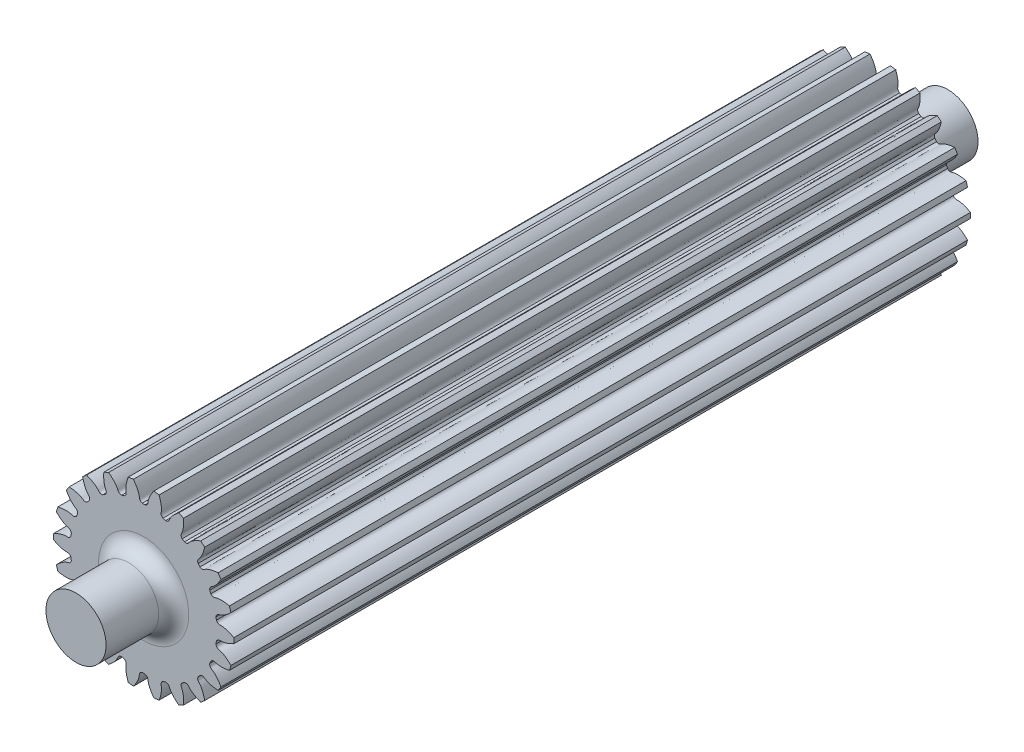
SolidWorks part; units mm, degrees
ref_plane "前视基准面" through (0, 0, 0) normal (0, 0, 1) x (1, 0, 0)
ref_plane "上视基准面" through (0, 0, 0) normal (0, 1, 0) x (1, 0, 0)
ref_plane "右视基准面" through (0, 0, 0) normal (1, 0, 0) x (0, 0, -1)
sketch "草图1" plane through (0, 0, 0) normal (0, 0, 1) x (1, 0, 0)
  circle A0 centre (0, 0) radius 12
extrude "凸台-拉伸1" add sketch "草图1" along normal blind 30
ref_axis "基准轴1" through (0, 0, -1.5) along (0, 0, 1)
sketch "草图2" plane through (0, 0, 0) normal (0, 0, 1) x (1, 0, 0)
  line L0 (0, 0) -> (0, 12) construction
  circle A0 centre (0, 0) radius 12 construction
  arc A1 (0.1857, 9.7482) -> (-0.1857, 9.7482) centre (0, 0) ccw
  arc A2 (3.0856, 13.5599) -> (-3.0856, 13.5599) centre (0, 0) ccw
  spline S0 degree 3 poles (0.1857, 9.7482) (0.5882, 9.8762) (0.5483, 10.1518) (0.5996, 10.4216) (0.606, 10.4519) (0.6139, 10.4862) (0.6235, 10.5243) (0.6349, 10.5661) (0.6484, 10.6117) (0.664, 10.661) (0.6819, 10.7139) (0.7023, 10.7703) (0.7253, 10.8301) (0.7511, 10.8933) (0.7797, 10.9597) (0.8114, 11.0293) (0.8462, 11.1021) (0.8843, 11.1778) (0.9259, 11.2563) (0.9711, 11.3377) (1.0199, 11.4217) (1.0726, 11.5082) (1.1292, 11.5972) (1.1899, 11.6884) (1.2547, 11.7818) (1.3238, 11.8773) (1.3973, 11.9746) (1.4753, 12.0737) (1.5579, 12.1744) (1.6452, 12.2766) (1.7372, 12.3802) (1.8341, 12.4849) (1.9359, 12.5906) (2.0428, 12.6972) (2.1547, 12.8044) (2.2718, 12.9123) (2.3942, 13.0205) (2.5218, 13.1289) (2.6548, 13.2373) (2.8415, 13.3834) (2.9864, 13.49) (3.0856, 13.5599) knots 0 0 0 0 0.157021 0.162531 0.168888 0.176093 0.184146 0.193046 0.202794 0.213389 0.224833 0.237123 0.250262 0.264248 0.279082 0.294763 0.311292 0.328669 0.346893 0.365965 0.385884 0.406652 0.428266 0.450729 0.474039 0.498197 0.523202 0.549055 0.575756 0.603304 0.6317 0.660944 0.691035 0.721974 0.75376 0.786395 0.819876 0.854206 0.889383 0.925408 1 1 1 1
  spline S1 degree 3 poles (-0.1857, 9.7482) (-0.5882, 9.8762) (-0.5483, 10.1518) (-0.5996, 10.4216) (-0.606, 10.4519) (-0.6139, 10.4862) (-0.6235, 10.5243) (-0.6349, 10.5661) (-0.6484, 10.6117) (-0.664, 10.661) (-0.6819, 10.7139) (-0.7023, 10.7703) (-0.7253, 10.8301) (-0.7511, 10.8933) (-0.7797, 10.9597) (-0.8114, 11.0293) (-0.8462, 11.1021) (-0.8843, 11.1778) (-0.9259, 11.2563) (-0.9711, 11.3377) (-1.0199, 11.4217) (-1.0726, 11.5082) (-1.1292, 11.5972) (-1.1899, 11.6884) (-1.2547, 11.7818) (-1.3238, 11.8773) (-1.3973, 11.9746) (-1.4753, 12.0737) (-1.5579, 12.1744) (-1.6452, 12.2766) (-1.7372, 12.3802) (-1.8341, 12.4849) (-1.9359, 12.5906) (-2.0428, 12.6972) (-2.1547, 12.8044) (-2.2718, 12.9123) (-2.3942, 13.0205) (-2.5218, 13.1289) (-2.6548, 13.2373) (-2.8415, 13.3834) (-2.9864, 13.49) (-3.0856, 13.5599) knots 0 0 0 0 0.157021 0.162531 0.168888 0.176093 0.184146 0.193046 0.202794 0.213389 0.224833 0.237123 0.250262 0.264248 0.279082 0.294763 0.311292 0.328669 0.346893 0.365965 0.385884 0.406652 0.428266 0.450729 0.474039 0.498197 0.523202 0.549055 0.575756 0.603304 0.6317 0.660944 0.691035 0.721974 0.75376 0.786395 0.819876 0.854206 0.889383 0.925408 1 1 1 1
extrude "切除-拉伸1" cut sketch "草图2" along normal through all
pattern_circular "阵列(圆周)1" count 22 every 16.364 about axis through (0, 0, -1.5) along (0, 0, 1) of "切除-拉伸1"
sketch "草图3" plane through (0, 0, 0) normal (0, 0, 1) x (1, 0, 0)
  circle A0 centre (0, 0) radius 11 construction
  dimension "Dn" = 22
sketch "草图4" plane through (0, 0, 0) normal (0, 0, -1) x (-1, 0, 0)
  arc A45 (2.9245, 9.3011) -> (2.5682, 9.4057) centre (0, 0) ccw
  arc A46 (2.0557, 11.8226) -> (1.3584, 11.9229) centre (0, 0) ccw
  arc A47 (0.1857, 9.7482) -> (-0.1857, 9.7482) centre (0, 0) ccw
  arc A48 (-1.3584, 11.9229) -> (-2.0557, 11.8226) centre (0, 0) ccw
  arc A49 (-2.5682, 9.4057) -> (-2.9245, 9.3011) centre (0, 0) ccw
  arc A50 (-4.6624, 11.0572) -> (-5.3032, 10.7646) centre (0, 0) ccw
  arc A51 (-5.1141, 8.3011) -> (-5.4265, 8.1004) centre (0, 0) ccw
  arc A52 (-7.5887, 9.2958) -> (-8.1211, 8.8344) centre (0, 0) ccw
  arc A53 (-7.2456, 6.5241) -> (-7.4888, 6.2434) centre (0, 0) ccw
  arc A54 (-9.9003, 6.7812) -> (-10.2811, 6.1886) centre (0, 0) ccw
  arc A55 (-8.7902, 4.2184) -> (-8.9444, 3.8807) centre (0, 0) ccw
  arc A56 (-11.4097, 3.7173) -> (-11.6082, 3.0414) centre (0, 0) ccw
  arc A57 (-9.6226, 1.5711) -> (-9.6754, 1.2035) centre (0, 0) ccw
  arc A58 (-11.9948, 0.3522) -> (-11.9948, -0.3522) centre (0, 0) ccw
  arc A59 (-9.6754, -1.2035) -> (-9.6226, -1.5711) centre (0, 0) ccw
  arc A60 (-11.6082, -3.0414) -> (-11.4097, -3.7173) centre (0, 0) ccw
  arc A61 (-8.9444, -3.8807) -> (-8.7902, -4.2184) centre (0, 0) ccw
  arc A62 (-10.2811, -6.1886) -> (-9.9003, -6.7812) centre (0, 0) ccw
  arc A63 (-7.4888, -6.2434) -> (-7.2456, -6.5241) centre (0, 0) ccw
  arc A64 (-8.1211, -8.8344) -> (-7.5887, -9.2958) centre (0, 0) ccw
  arc A65 (-5.4265, -8.1004) -> (-5.1141, -8.3011) centre (0, 0) ccw
  arc A66 (-5.3032, -10.7646) -> (-4.6624, -11.0572) centre (0, 0) ccw
  arc A67 (-2.9245, -9.3011) -> (-2.5682, -9.4057) centre (0, 0) ccw
  arc A68 (-2.0557, -11.8226) -> (-1.3584, -11.9229) centre (0, 0) ccw
  arc A69 (-0.1857, -9.7482) -> (0.1857, -9.7482) centre (0, 0) ccw
  arc A70 (1.3584, -11.9229) -> (2.0557, -11.8226) centre (0, 0) ccw
  arc A71 (2.5682, -9.4057) -> (2.9245, -9.3011) centre (0, 0) ccw
  arc A72 (4.6624, -11.0572) -> (5.3032, -10.7646) centre (0, 0) ccw
  arc A73 (5.1141, -8.3011) -> (5.4265, -8.1004) centre (0, 0) ccw
  arc A74 (7.5887, -9.2958) -> (8.1211, -8.8344) centre (0, 0) ccw
  arc A75 (7.2456, -6.5241) -> (7.4888, -6.2434) centre (0, 0) ccw
  arc A76 (9.9003, -6.7812) -> (10.2811, -6.1886) centre (0, 0) ccw
  arc A77 (8.7902, -4.2184) -> (8.9444, -3.8807) centre (0, 0) ccw
  arc A78 (11.4097, -3.7173) -> (11.6082, -3.0414) centre (0, 0) ccw
  arc A79 (9.6226, -1.5711) -> (9.6754, -1.2035) centre (0, 0) ccw
  arc A80 (11.9948, -0.3522) -> (11.9948, 0.3522) centre (0, 0) ccw
  arc A81 (9.6754, 1.2035) -> (9.6226, 1.5711) centre (0, 0) ccw
  arc A82 (11.6082, 3.0414) -> (11.4097, 3.7173) centre (0, 0) ccw
  arc A83 (8.9444, 3.8807) -> (8.7902, 4.2184) centre (0, 0) ccw
  arc A84 (10.2811, 6.1886) -> (9.9003, 6.7812) centre (0, 0) ccw
  arc A85 (7.4888, 6.2434) -> (7.2456, 6.5241) centre (0, 0) ccw
  arc A86 (8.1211, 8.8344) -> (7.5887, 9.2958) centre (0, 0) ccw
  arc A87 (5.4265, 8.1004) -> (5.1141, 8.3011) centre (0, 0) ccw
  arc A88 (5.3032, 10.7646) -> (4.6624, 11.0572) centre (0, 0) ccw
  arc A89 (2.9245, 9.3011) -> (2.5682, 9.4057) centre (0, 0) ccw
  arc A90 (2.0557, 11.8226) -> (1.3584, 11.9229) centre (0, 0) ccw
  arc A91 (0.1857, 9.7482) -> (-0.1857, 9.7482) centre (0, 0) ccw
  arc A92 (-1.3584, 11.9229) -> (-2.0557, 11.8226) centre (0, 0) ccw
  arc A93 (-2.5682, 9.4057) -> (-2.9245, 9.3011) centre (0, 0) ccw
  arc A94 (-4.6624, 11.0572) -> (-5.3032, 10.7646) centre (0, 0) ccw
  arc A95 (-5.1141, 8.3011) -> (-5.4265, 8.1004) centre (0, 0) ccw
  arc A96 (-7.5887, 9.2958) -> (-8.1211, 8.8344) centre (0, 0) ccw
  arc A97 (-7.2456, 6.5241) -> (-7.4888, 6.2434) centre (0, 0) ccw
  arc A98 (-9.9003, 6.7812) -> (-10.2811, 6.1886) centre (0, 0) ccw
  arc A99 (-8.7902, 4.2184) -> (-8.9444, 3.8807) centre (0, 0) ccw
  arc A100 (-11.4097, 3.7173) -> (-11.6082, 3.0414) centre (0, 0) ccw
  arc A101 (-9.6226, 1.5711) -> (-9.6754, 1.2035) centre (0, 0) ccw
  arc A102 (-11.9948, 0.3522) -> (-11.9948, -0.3522) centre (0, 0) ccw
  arc A103 (-9.6754, -1.2035) -> (-9.6226, -1.5711) centre (0, 0) ccw
  arc A104 (-11.6082, -3.0414) -> (-11.4097, -3.7173) centre (0, 0) ccw
  arc A105 (-8.9444, -3.8807) -> (-8.7902, -4.2184) centre (0, 0) ccw
  arc A106 (-10.2811, -6.1886) -> (-9.9003, -6.7812) centre (0, 0) ccw
  arc A107 (-7.4888, -6.2434) -> (-7.2456, -6.5241) centre (0, 0) ccw
  arc A108 (-8.1211, -8.8344) -> (-7.5887, -9.2958) centre (0, 0) ccw
  arc A109 (-5.4265, -8.1004) -> (-5.1141, -8.3011) centre (0, 0) ccw
  arc A110 (-5.3032, -10.7646) -> (-4.6624, -11.0572) centre (0, 0) ccw
  arc A111 (-2.9245, -9.3011) -> (-2.5682, -9.4057) centre (0, 0) ccw
  arc A112 (-2.0557, -11.8226) -> (-1.3584, -11.9229) centre (0, 0) ccw
  arc A113 (-0.1857, -9.7482) -> (0.1857, -9.7482) centre (0, 0) ccw
  arc A114 (1.3584, -11.9229) -> (2.0557, -11.8226) centre (0, 0) ccw
  arc A115 (2.5682, -9.4057) -> (2.9245, -9.3011) centre (0, 0) ccw
  arc A116 (4.6624, -11.0572) -> (5.3032, -10.7646) centre (0, 0) ccw
  arc A117 (5.1141, -8.3011) -> (5.4265, -8.1004) centre (0, 0) ccw
  arc A118 (7.5887, -9.2958) -> (8.1211, -8.8344) centre (0, 0) ccw
  arc A119 (7.2456, -6.5241) -> (7.4888, -6.2434) centre (0, 0) ccw
  arc A120 (9.9003, -6.7812) -> (10.2811, -6.1886) centre (0, 0) ccw
  arc A121 (8.7902, -4.2184) -> (8.9444, -3.8807) centre (0, 0) ccw
  arc A122 (11.4097, -3.7173) -> (11.6082, -3.0414) centre (0, 0) ccw
  arc A123 (9.6226, -1.5711) -> (9.6754, -1.2035) centre (0, 0) ccw
  arc A124 (11.9948, -0.3522) -> (11.9948, 0.3522) centre (0, 0) ccw
  arc A125 (9.6754, 1.2035) -> (9.6226, 1.5711) centre (0, 0) ccw
  arc A126 (11.6082, 3.0414) -> (11.4097, 3.7173) centre (0, 0) ccw
  arc A127 (8.9444, 3.8807) -> (8.7902, 4.2184) centre (0, 0) ccw
  arc A128 (10.2811, 6.1886) -> (9.9003, 6.7812) centre (0, 0) ccw
  arc A129 (7.4888, 6.2434) -> (7.2456, 6.5241) centre (0, 0) ccw
  arc A130 (8.1211, 8.8344) -> (7.5887, 9.2958) centre (0, 0) ccw
  arc A131 (5.4265, 8.1004) -> (5.1141, 8.3011) centre (0, 0) ccw
  arc A132 (5.3032, 10.7646) -> (4.6624, 11.0572) centre (0, 0) ccw
  spline S44 degree 3 poles (-9364.1406, 3504.5844) (256.9535, -188.5881) (30.391, 33.0955) (4.2738, 10.7434) (4.1283, 10.6084) (3.9999, 10.4794) (3.888, 10.3576) (3.7917, 10.2441) (3.7102, 10.1398) (3.6518, 10.0587) (3.6037, 9.9872) (3.5713, 9.9359) (3.5381, 9.8795) (3.5167, 9.8409) (0.4171, 3.7881) (50.6224, -28.8281) (-8414.4505, 5403.2739) knots -20.504077 -20.504077 -20.504077 -20.504077 0.549271 0.593348 0.634035 0.671331 0.705237 0.735752 0.762877 0.786611 0.797206 0.815854 0.823907 0.837469 0.842979 5.006087 5.006087 5.006087 5.006087 only from (4.6624, 11.0572) to (2.9245, 9.3011)
  spline S45 degree 3 poles (9998.4358, -3.6711) (-58.166, 3.1168) (1.6971, 3.4126) (2.3619, 10.18) (2.3658, 10.2385) (2.3681, 10.3211) (2.3668, 10.4204) (2.3608, 10.536) (2.3486, 10.6678) (2.329, 10.8154) (2.3007, 10.9784) (2.2624, 11.1562) (2.213, 11.3485) (2.1511, 11.5544) (-9.7414, 46.086) (-333.2574, -33.7791) (9782.7718, -2064.5446) knots -4.005883 -4.005883 -4.005883 -4.005883 0.157021 0.162531 0.176093 0.193046 0.213389 0.237123 0.264248 0.294763 0.328669 0.365965 0.406652 0.450729 0.498197 22.864222 22.864222 22.864222 22.864222 only from (2.5682, 9.4057) to (2.0557, 11.8226)
  spline S46 degree 3 poles (-9972.1826, 724.4408) (299.6765, -108.5568) (19.8359, 40.317) (1.0739, 11.5123) (0.9723, 11.3417) (0.8855, 11.1818) (0.8124, 11.0334) (0.752, 10.8973) (0.7032, 10.7743) (0.6701, 10.6801) (0.644, 10.5979) (0.6274, 10.5396) (0.6113, 10.4761) (0.6018, 10.4331) (-0.667, 3.7521) (56.6936, -13.3983) (-9595.8843, 2813.7787) knots -20.504077 -20.504077 -20.504077 -20.504077 0.549271 0.593348 0.634035 0.671331 0.705237 0.735752 0.762877 0.786611 0.797206 0.815854 0.823907 0.837469 0.842979 5.006087 5.006087 5.006087 5.006087 only from (1.3584, 11.9229) to (0.1857, 9.7482)
  spline S47 degree 3 poles (9594.4631, 2813.3625) (-56.688, -13.3967) (0.6669, 3.7525) (-0.6018, 10.4331) (-0.6145, 10.4903) (-0.6356, 10.5702) (-0.6648, 10.6651) (-0.7032, 10.7743) (-0.752, 10.8973) (-0.8124, 11.0334) (-0.8855, 11.1818) (-0.9723, 11.3417) (-1.0739, 11.5123) (-1.1913, 11.6924) (-22.3307, 41.4748) (-310.2415, -126.3003) (9968.1502, 775.2093) knots -4.005883 -4.005883 -4.005883 -4.005883 0.157021 0.162531 0.176093 0.193046 0.213389 0.237123 0.264248 0.294763 0.328669 0.365965 0.406652 0.450729 0.498197 22.864222 22.864222 22.864222 22.864222 only from (-0.1857, 9.7482) to (-1.3584, 11.9229)
  spline S48 degree 3 poles (-9772.3377, -2114.3927) (318.1215, -19.7309) (7.6738, 44.2723) (-2.213, 11.3485) (-2.2624, 11.1562) (-2.3007, 10.9784) (-2.329, 10.8154) (-2.3486, 10.6678) (-2.3608, 10.536) (-2.366, 10.4362) (-2.3678, 10.3501) (-2.3674, 10.2894) (-2.3649, 10.224) (-2.3619, 10.18) (-1.6971, 3.4122) (58.1719, 3.1168) (-9999.9166, -3.6721) knots -20.504077 -20.504077 -20.504077 -20.504077 0.549271 0.593348 0.634035 0.671331 0.705237 0.735752 0.762877 0.786611 0.797206 0.815854 0.823907 0.837469 0.842979 5.006087 5.006087 5.006087 5.006087 only from (-2.0557, 11.8226) to (-2.5682, 9.4057)
  spline S49 degree 3 poles (8413.2042, 5402.4742) (-50.6175, -28.8249) (-0.4173, 3.7884) (-3.5167, 9.8409) (-3.5451, 9.8922) (-3.5879, 9.963) (-3.6426, 10.0458) (-3.7102, 10.1398) (-3.7917, 10.2441) (-3.888, 10.3576) (-3.9999, 10.4794) (-4.1283, 10.6084) (-4.2738, 10.7434) (-4.4372, 10.8832) (-33.111, 33.5035) (-262.0916, -208.5894) (9345.9684, 3552.1603) knots -4.005883 -4.005883 -4.005883 -4.005883 0.157021 0.162531 0.176093 0.193046 0.213389 0.237123 0.264248 0.294763 0.328669 0.365965 0.406652 0.450729 0.498197 22.864222 22.864222 22.864222 22.864222 only from (-2.9245, 9.3011) to (-4.6624, 11.0572)
  spline S50 degree 3 poles (-8780.7961, -4781.9306) (310.7942, 70.6936) (-5.11, 44.6409) (-5.3206, 10.2653) (-5.3138, 10.0669) (-5.3004, 9.8855) (-5.2817, 9.7211) (-5.2589, 9.574) (-5.2335, 9.4441) (-5.2104, 9.3469) (-5.1879, 9.2637) (-5.1704, 9.2057) (-5.1495, 9.1436) (-5.1343, 9.1022) (-2.5897, 2.7959) (54.9374, 19.3795) (-9593.8152, -2820.8254) knots -20.504077 -20.504077 -20.504077 -20.504077 0.549271 0.593348 0.634035 0.671331 0.705237 0.735752 0.762877 0.786611 0.797206 0.815854 0.823907 0.837469 0.842979 5.006087 5.006087 5.006087 5.006087 only from (-5.3032, 10.7646) to (-5.1141, 8.3011)
  spline S51 degree 3 poles (6550.3574, 7553.9095) (-40.4462, -41.9178) (-1.4677, 3.5173) (-6.1468, 8.4515) (-6.1884, 8.4928) (-6.2494, 8.5486) (-6.3253, 8.6126) (-6.4166, 8.6838) (-6.5242, 8.7609) (-6.6486, 8.8427) (-6.7903, 8.928) (-6.9498, 9.0156) (-7.1274, 9.1041) (-7.3236, 9.1923) (-41.2087, 22.8179) (-192.7087, -273.9798) (7966.6318, 6041.3364) knots -4.005883 -4.005883 -4.005883 -4.005883 0.157021 0.162531 0.176093 0.193046 0.213389 0.237123 0.264248 0.294763 0.328669 0.365965 0.406652 0.450729 0.498197 22.864222 22.864222 22.864222 22.864222 only from (-5.4265, 8.1004) to (-7.5887, 9.2958)
  spline S52 degree 3 poles (-7077.8866, -7062.0649) (278.2882, 155.3908) (-17.4798, 41.393) (-7.9971, 8.3505) (-7.9348, 8.1621) (-7.8708, 7.9917) (-7.8065, 7.8393) (-7.7432, 7.7046) (-7.6822, 7.5871) (-7.6327, 7.5003) (-7.5876, 7.4269) (-7.5545, 7.3761) (-7.517, 7.3224) (-7.4907, 7.287) (-3.2725, 1.953) (47.2522, 34.0721) (-8410.4799, -5409.4523) knots -20.504077 -20.504077 -20.504077 -20.504077 0.549271 0.593348 0.634035 0.671331 0.705237 0.735752 0.762877 0.786611 0.797206 0.815854 0.823907 0.837469 0.842979 5.006087 5.006087 5.006087 5.006087 only from (-8.1211, 8.8344) to (-7.2456, 6.5241)
  spline S53 degree 3 poles (4156.8397, 9093.3721) (-26.9982, -51.6149) (-2.3992, 2.9614) (-8.2789, 6.3774) (-8.3304, 6.4053) (-8.4047, 6.4416) (-8.4955, 6.4817) (-8.6032, 6.5243) (-8.7281, 6.5679) (-8.8705, 6.6114) (-9.0305, 6.6533) (-9.2082, 6.6924) (-9.4036, 6.7273) (-9.6167, 6.7566) (-45.968, 10.2838) (-107.7136, -317.174) (5941.8861, 8041.0794) knots -4.005883 -4.005883 -4.005883 -4.005883 0.157021 0.162531 0.176093 0.193046 0.213389 0.237123 0.264248 0.294763 0.328669 0.365965 0.406652 0.450729 0.498197 22.864222 22.864222 22.864222 22.864222 only from (-7.4888, 6.2434) to (-9.9003, 6.7812)
  spline S54 degree 3 poles (-4801.5689, -8770.0728) (223.2369, 227.4992) (-28.4335, 34.7917) (-10.0258, 5.7592) (-9.9129, 5.596) (-9.8035, 5.4506) (-9.6989, 5.3224) (-9.6002, 5.211) (-9.5086, 5.1155) (-9.4366, 5.0462) (-9.3727, 4.9884) (-9.3266, 4.949) (-9.2755, 4.908) (-9.2403, 4.8814) (-3.6901, 0.952) (35.7389, 46.0045) (-6545.7775, -7559.8374) knots -20.504077 -20.504077 -20.504077 -20.504077 0.549271 0.593348 0.634035 0.671331 0.705237 0.735752 0.762877 0.786611 0.797206 0.815854 0.823907 0.837469 0.842979 5.006087 5.006087 5.006087 5.006087 only from (-10.2811, 6.1886) to (-8.7902, 4.2184)
  spline S55 degree 3 poles (1426.5595, 9896.1437) (-11.363, -57.1304) (-3.1363, 2.1655) (-9.7402, 3.7867) (-9.7976, 3.7989) (-9.8791, 3.8128) (-9.9775, 3.8257) (-10.0928, 3.8362) (-10.225, 3.8429) (-10.3738, 3.8445) (-10.5392, 3.8396) (-10.7207, 3.8271) (-10.918, 3.8055) (-11.1307, 3.7736) (-47.0033, -3.0835) (-13.9922, -334.6726) (3435.7641, 9389.3819) knots -4.005883 -4.005883 -4.005883 -4.005883 0.157021 0.162531 0.176093 0.193046 0.213389 0.237123 0.264248 0.294763 0.328669 0.365965 0.406652 0.450729 0.498197 22.864222 22.864222 22.864222 22.864222 only from (-8.9444, 3.8807) to (-11.4097, 3.7173)
  spline S56 degree 3 poles (-2136.2566, -9767.5815) (150.1003, 281.177) (-37.0837, 25.3717) (-11.2422, 2.7013) (-11.0879, 2.5765) (-10.942, 2.4678) (-10.8055, 2.3743) (-10.6794, 2.2952) (-10.5646, 2.2294) (-10.476, 2.1832) (-10.3984, 2.1457) (-10.3431, 2.1209) (-10.2825, 2.096) (-10.2412, 2.0804) (-3.8089, -0.1262) (21.3303, 54.2098) (-4150.7752, -9097.7696) knots -20.504077 -20.504077 -20.504077 -20.504077 0.549271 0.593348 0.634035 0.671331 0.705237 0.735752 0.762877 0.786611 0.797206 0.815854 0.823907 0.837469 0.842979 5.006087 5.006087 5.006087 5.006087 only from (-11.6082, 3.0414) to (-9.6226, 1.5711)
  spline S57 degree 3 poles (-1419.292, 9897.1886) (5.1928, -58.0175) (-3.6193, 1.1942) (-10.4125, 0.8891) (-10.4709, 0.8847) (-10.5531, 0.8751) (-10.6512, 0.8598) (-10.7647, 0.8373) (-10.8934, 0.8065) (-11.0367, 0.7661) (-11.194, 0.7149) (-11.3647, 0.6517) (-11.5479, 0.5754) (-11.743, 0.4849) (-44.2306, -16.2009) (80.8628, -325.0581) (651.2969, 9977.0126) knots -4.005883 -4.005883 -4.005883 -4.005883 0.157021 0.162531 0.176093 0.193046 0.213389 0.237123 0.264248 0.294763 0.328669 0.365965 0.406652 0.450729 0.498197 22.864222 22.864222 22.864222 22.864222 only from (-9.6754, 1.2035) to (-11.9948, 0.3522)
  spline S58 degree 3 poles (702.1225, -9973.7788) (64.8035, 312.0755) (-42.7296, 13.8963) (-11.5479, -0.5754) (-11.3647, -0.6517) (-11.194, -0.7149) (-11.0367, -0.7661) (-10.8934, -0.8065) (-10.7647, -0.8373) (-10.6667, -0.8567) (-10.5817, -0.8708) (-10.5216, -0.879) (-10.4565, -0.8858) (-10.4125, -0.8891) (-3.619, -1.1942) (5.1936, 58.0233) (-1419.5018, -9898.6545) knots -20.504077 -20.504077 -20.504077 -20.504077 0.549271 0.593348 0.634035 0.671331 0.705237 0.735752 0.762877 0.786611 0.797206 0.815854 0.823907 0.837469 0.842979 5.006087 5.006087 5.006087 5.006087 only from (-11.9948, -0.3522) to (-9.6754, -1.2035)
  spline S59 degree 3 poles (-4150.161, 9096.4221) (21.3278, -54.2044) (-3.8092, 0.1261) (-10.2412, -2.0804) (-10.296, -2.1012) (-10.3722, -2.1335) (-10.4619, -2.1758) (-10.5646, -2.2294) (-10.6794, -2.2952) (-10.8055, -2.3743) (-10.942, -2.4678) (-11.0879, -2.5765) (-11.2422, -2.7014) (-11.4039, -2.8432) (-37.8746, -28.0059) (169.1667, -289.1093) (-2185.9344, 9756.365) knots -4.005883 -4.005883 -4.005883 -4.005883 0.157021 0.162531 0.176093 0.193046 0.213389 0.237123 0.264248 0.294763 0.328669 0.365965 0.406652 0.450729 0.498197 22.864222 22.864222 22.864222 22.864222 only from (-9.6226, -1.5711) to (-11.6082, -3.0414)
  spline S60 degree 3 poles (3483.6198, -9371.9599) (-25.7434, 317.6915) (-44.9138, 1.2951) (-10.918, -3.8055) (-10.7207, -3.8271) (-10.5392, -3.8396) (-10.3738, -3.8445) (-10.225, -3.8429) (-10.0928, -3.8362) (-9.9933, -3.8272) (-9.9078, -3.8167) (-9.8478, -3.8076) (-9.7834, -3.7958) (-9.7402, -3.7867) (-3.136, -2.1654) (-11.3638, 57.1362) (1426.7712, -9897.6093) knots -20.504077 -20.504077 -20.504077 -20.504077 0.549271 0.593348 0.634035 0.671331 0.705237 0.735752 0.762877 0.786611 0.797206 0.815854 0.823907 0.837469 0.842979 5.006087 5.006087 5.006087 5.006087 only from (-11.4097, -3.7173) to (-8.9444, -3.8807)
  spline S61 degree 3 poles (-6544.8086, 7558.7176) (35.7351, -46) (-3.6904, -0.9522) (-9.2403, -4.8814) (-9.287, -4.9168) (-9.351, -4.9692) (-9.4251, -5.0352) (-9.5086, -5.1155) (-9.6002, -5.211) (-9.6989, -5.3224) (-9.8035, -5.4506) (-9.9129, -5.596) (-10.0258, -5.7592) (-10.1409, -5.9408) (-28.4503, -37.542) (243.7658, -229.7385) (-4846.0744, 8745.3148) knots -4.005883 -4.005883 -4.005883 -4.005883 0.157021 0.162531 0.176093 0.193046 0.213389 0.237123 0.264248 0.294763 0.328669 0.365965 0.406652 0.450729 0.498197 22.864222 22.864222 22.864222 22.864222 only from (-8.7902, -4.2184) to (-10.2811, -6.1886)
  spline S62 degree 3 poles (5982.895, -8010.8806) (-114.2046, 297.57) (-43.4593, -11.4111) (-9.4036, -6.7273) (-9.2082, -6.6924) (-9.0305, -6.6533) (-8.8705, -6.6114) (-8.7281, -6.5679) (-8.6032, -6.5243) (-8.5102, -6.4876) (-8.4311, -6.4535) (-8.3761, -6.4279) (-8.3177, -6.3984) (-8.2789, -6.3774) (-2.3989, -2.9612) (-27.0006, 51.6202) (4157.4558, -9094.7187) knots -20.504077 -20.504077 -20.504077 -20.504077 0.549271 0.593348 0.634035 0.671331 0.705237 0.735752 0.762877 0.786611 0.797206 0.815854 0.823907 0.837469 0.842979 5.006087 5.006087 5.006087 5.006087 only from (-9.9003, -6.7812) to (-7.4888, -6.2434)
  spline S63 degree 3 poles (-8409.2347, 5408.6508) (47.2473, -34.069) (-3.2727, -1.9533) (-7.4907, -7.287) (-7.5256, -7.3341) (-7.5722, -7.4024) (-7.6248, -7.4866) (-7.6822, -7.5871) (-7.7432, -7.7046) (-7.8065, -7.8393) (-7.8708, -7.9917) (-7.9348, -8.1621) (-7.9971, -8.3505) (-8.0564, -8.5572) (-16.721, -44.0366) (298.6164, -151.7558) (-7113.6142, 7025.7712) knots -4.005883 -4.005883 -4.005883 -4.005883 0.157021 0.162531 0.176093 0.193046 0.213389 0.237123 0.264248 0.294763 0.328669 0.365965 0.406652 0.450729 0.498197 22.864222 22.864222 22.864222 22.864222 only from (-7.2456, -6.5241) to (-8.1211, -8.8344)
  spline S64 degree 3 poles (7997.4716, -6000.8073) (-193.4137, 253.3412) (-38.484, -23.1927) (-7.1274, -9.1041) (-6.9498, -9.0156) (-6.7903, -8.928) (-6.6486, -8.8427) (-6.5242, -8.7609) (-6.4166, -8.6838) (-6.3378, -8.6224) (-6.2715, -8.5674) (-6.2259, -8.5273) (-6.1781, -8.4826) (-6.1468, -8.4515) (-1.4674, -3.5171) (-40.45, 41.9223) (6551.3279, -7555.028) knots -20.504077 -20.504077 -20.504077 -20.504077 0.549271 0.593348 0.634035 0.671331 0.705237 0.735752 0.762877 0.786611 0.797206 0.815854 0.823907 0.837469 0.842979 5.006087 5.006087 5.006087 5.006087 only from (-7.5887, -9.2958) to (-5.4265, -8.1004)
  spline S65 degree 3 poles (-9592.3946, 2820.4073) (54.9318, -19.3779) (-2.5898, -2.7962) (-5.1343, -9.1022) (-5.1545, -9.1572) (-5.18, -9.2359) (-5.2067, -9.3315) (-5.2335, -9.4441) (-5.2589, -9.574) (-5.2817, -9.7211) (-5.3004, -9.8855) (-5.3138, -10.0669) (-5.3206, -10.2653) (-5.3192, -10.4804) (-3.6372, -46.9637) (329.2748, -61.4786) (-8804.8513, 4737.0413) knots -4.005883 -4.005883 -4.005883 -4.005883 0.157021 0.162531 0.176093 0.193046 0.213389 0.237123 0.264248 0.294763 0.328669 0.365965 0.406652 0.450729 0.498197 22.864222 22.864222 22.864222 22.864222 only from (-5.1141, -8.3011) to (-5.3032, -10.7646)
  spline S66 degree 3 poles (9364.1406, -3504.5844) (-256.9535, 188.5881) (-30.391, -33.0955) (-4.2738, -10.7434) (-4.1283, -10.6084) (-3.9999, -10.4794) (-3.888, -10.3576) (-3.7917, -10.2441) (-3.7102, -10.1398) (-3.6518, -10.0587) (-3.6037, -9.9872) (-3.5713, -9.9359) (-3.5381, -9.8795) (-3.5167, -9.8409) (-0.4171, -3.7881) (-50.6224, 28.8281) (8414.4505, -5403.2739) knots -20.504077 -20.504077 -20.504077 -20.504077 0.549271 0.593348 0.634035 0.671331 0.705237 0.735752 0.762877 0.786611 0.797206 0.815854 0.823907 0.837469 0.842979 5.006087 5.006087 5.006087 5.006087 only from (-4.6624, -11.0572) to (-2.9245, -9.3011)
  spline S67 degree 3 poles (-9998.4358, 3.6711) (58.166, -3.1168) (-1.6971, -3.4126) (-2.3619, -10.18) (-2.3658, -10.2385) (-2.3681, -10.3211) (-2.3668, -10.4204) (-2.3608, -10.536) (-2.3486, -10.6678) (-2.329, -10.8154) (-2.3007, -10.9784) (-2.2624, -11.1562) (-2.213, -11.3485) (-2.1511, -11.5544) (9.7414, -46.086) (333.2574, 33.7791) (-9782.7718, 2064.5446) knots -4.005883 -4.005883 -4.005883 -4.005883 0.157021 0.162531 0.176093 0.193046 0.213389 0.237123 0.264248 0.294763 0.328669 0.365965 0.406652 0.450729 0.498197 22.864222 22.864222 22.864222 22.864222 only from (-2.5682, -9.4057) to (-2.0557, -11.8226)
  spline S68 degree 3 poles (9972.1826, -724.4408) (-299.6765, 108.5568) (-19.8359, -40.317) (-1.0739, -11.5123) (-0.9723, -11.3417) (-0.8855, -11.1818) (-0.8124, -11.0334) (-0.752, -10.8973) (-0.7032, -10.7743) (-0.6701, -10.6801) (-0.644, -10.5979) (-0.6274, -10.5396) (-0.6113, -10.4761) (-0.6018, -10.4331) (0.667, -3.7521) (-56.6936, 13.3983) (9595.8843, -2813.7787) knots -20.504077 -20.504077 -20.504077 -20.504077 0.549271 0.593348 0.634035 0.671331 0.705237 0.735752 0.762877 0.786611 0.797206 0.815854 0.823907 0.837469 0.842979 5.006087 5.006087 5.006087 5.006087 only from (-1.3584, -11.9229) to (-0.1857, -9.7482)
  spline S69 degree 3 poles (-9594.4631, -2813.3625) (56.688, 13.3967) (-0.6669, -3.7525) (0.6018, -10.4331) (0.6145, -10.4903) (0.6356, -10.5702) (0.6648, -10.6651) (0.7032, -10.7743) (0.752, -10.8973) (0.8124, -11.0334) (0.8855, -11.1818) (0.9723, -11.3417) (1.0739, -11.5123) (1.1913, -11.6924) (22.3307, -41.4748) (310.2415, 126.3003) (-9968.1502, -775.2093) knots -4.005883 -4.005883 -4.005883 -4.005883 0.157021 0.162531 0.176093 0.193046 0.213389 0.237123 0.264248 0.294763 0.328669 0.365965 0.406652 0.450729 0.498197 22.864222 22.864222 22.864222 22.864222 only from (0.1857, -9.7482) to (1.3584, -11.9229)
  spline S70 degree 3 poles (9772.3377, 2114.3927) (-318.1215, 19.7309) (-7.6738, -44.2723) (2.213, -11.3485) (2.2624, -11.1562) (2.3007, -10.9784) (2.329, -10.8154) (2.3486, -10.6678) (2.3608, -10.536) (2.366, -10.4362) (2.3678, -10.3501) (2.3674, -10.2894) (2.3649, -10.224) (2.3619, -10.18) (1.6971, -3.4122) (-58.1719, -3.1168) (9999.9166, 3.6721) knots -20.504077 -20.504077 -20.504077 -20.504077 0.549271 0.593348 0.634035 0.671331 0.705237 0.735752 0.762877 0.786611 0.797206 0.815854 0.823907 0.837469 0.842979 5.006087 5.006087 5.006087 5.006087 only from (2.0557, -11.8226) to (2.5682, -9.4057)
  spline S71 degree 3 poles (-8413.2042, -5402.4742) (50.6175, 28.8249) (0.4173, -3.7884) (3.5167, -9.8409) (3.5451, -9.8922) (3.5879, -9.963) (3.6426, -10.0458) (3.7102, -10.1398) (3.7917, -10.2441) (3.888, -10.3576) (3.9999, -10.4794) (4.1283, -10.6084) (4.2738, -10.7434) (4.4372, -10.8832) (33.111, -33.5035) (262.0916, 208.5894) (-9345.9684, -3552.1603) knots -4.005883 -4.005883 -4.005883 -4.005883 0.157021 0.162531 0.176093 0.193046 0.213389 0.237123 0.264248 0.294763 0.328669 0.365965 0.406652 0.450729 0.498197 22.864222 22.864222 22.864222 22.864222 only from (2.9245, -9.3011) to (4.6624, -11.0572)
  spline S72 degree 3 poles (8780.7961, 4781.9306) (-310.7942, -70.6936) (5.11, -44.6409) (5.3206, -10.2653) (5.3138, -10.0669) (5.3004, -9.8855) (5.2817, -9.7211) (5.2589, -9.574) (5.2335, -9.4441) (5.2104, -9.3469) (5.1879, -9.2637) (5.1704, -9.2057) (5.1495, -9.1436) (5.1343, -9.1022) (2.5897, -2.7959) (-54.9374, -19.3795) (9593.8152, 2820.8254) knots -20.504077 -20.504077 -20.504077 -20.504077 0.549271 0.593348 0.634035 0.671331 0.705237 0.735752 0.762877 0.786611 0.797206 0.815854 0.823907 0.837469 0.842979 5.006087 5.006087 5.006087 5.006087 only from (5.3032, -10.7646) to (5.1141, -8.3011)
  spline S73 degree 3 poles (-6550.3574, -7553.9095) (40.4462, 41.9178) (1.4677, -3.5173) (6.1468, -8.4515) (6.1884, -8.4928) (6.2494, -8.5486) (6.3253, -8.6126) (6.4166, -8.6838) (6.5242, -8.7609) (6.6486, -8.8427) (6.7903, -8.928) (6.9498, -9.0156) (7.1274, -9.1041) (7.3236, -9.1923) (41.2087, -22.8179) (192.7087, 273.9798) (-7966.6318, -6041.3364) knots -4.005883 -4.005883 -4.005883 -4.005883 0.157021 0.162531 0.176093 0.193046 0.213389 0.237123 0.264248 0.294763 0.328669 0.365965 0.406652 0.450729 0.498197 22.864222 22.864222 22.864222 22.864222 only from (5.4265, -8.1004) to (7.5887, -9.2958)
  spline S74 degree 3 poles (7077.8866, 7062.0649) (-278.2882, -155.3908) (17.4798, -41.393) (7.9971, -8.3505) (7.9348, -8.1621) (7.8708, -7.9917) (7.8065, -7.8393) (7.7432, -7.7046) (7.6822, -7.5871) (7.6327, -7.5003) (7.5876, -7.4269) (7.5545, -7.3761) (7.517, -7.3224) (7.4907, -7.287) (3.2725, -1.953) (-47.2522, -34.0721) (8410.4799, 5409.4523) knots -20.504077 -20.504077 -20.504077 -20.504077 0.549271 0.593348 0.634035 0.671331 0.705237 0.735752 0.762877 0.786611 0.797206 0.815854 0.823907 0.837469 0.842979 5.006087 5.006087 5.006087 5.006087 only from (8.1211, -8.8344) to (7.2456, -6.5241)
  spline S75 degree 3 poles (-4156.8397, -9093.3721) (26.9982, 51.6149) (2.3992, -2.9614) (8.2789, -6.3774) (8.3304, -6.4053) (8.4047, -6.4416) (8.4955, -6.4817) (8.6032, -6.5243) (8.7281, -6.5679) (8.8705, -6.6114) (9.0305, -6.6533) (9.2082, -6.6924) (9.4036, -6.7273) (9.6167, -6.7566) (45.968, -10.2838) (107.7136, 317.174) (-5941.8861, -8041.0794) knots -4.005883 -4.005883 -4.005883 -4.005883 0.157021 0.162531 0.176093 0.193046 0.213389 0.237123 0.264248 0.294763 0.328669 0.365965 0.406652 0.450729 0.498197 22.864222 22.864222 22.864222 22.864222 only from (7.4888, -6.2434) to (9.9003, -6.7812)
  spline S76 degree 3 poles (4801.5689, 8770.0728) (-223.2369, -227.4992) (28.4335, -34.7917) (10.0258, -5.7592) (9.9129, -5.596) (9.8035, -5.4506) (9.6989, -5.3224) (9.6002, -5.211) (9.5086, -5.1155) (9.4366, -5.0462) (9.3727, -4.9884) (9.3266, -4.949) (9.2755, -4.908) (9.2403, -4.8814) (3.6901, -0.952) (-35.7389, -46.0045) (6545.7775, 7559.8374) knots -20.504077 -20.504077 -20.504077 -20.504077 0.549271 0.593348 0.634035 0.671331 0.705237 0.735752 0.762877 0.786611 0.797206 0.815854 0.823907 0.837469 0.842979 5.006087 5.006087 5.006087 5.006087 only from (10.2811, -6.1886) to (8.7902, -4.2184)
  spline S77 degree 3 poles (-1426.5595, -9896.1437) (11.363, 57.1304) (3.1363, -2.1655) (9.7402, -3.7867) (9.7976, -3.7989) (9.8791, -3.8128) (9.9775, -3.8257) (10.0928, -3.8362) (10.225, -3.8429) (10.3738, -3.8445) (10.5392, -3.8396) (10.7207, -3.8271) (10.918, -3.8055) (11.1307, -3.7736) (47.0033, 3.0835) (13.9922, 334.6726) (-3435.7641, -9389.3819) knots -4.005883 -4.005883 -4.005883 -4.005883 0.157021 0.162531 0.176093 0.193046 0.213389 0.237123 0.264248 0.294763 0.328669 0.365965 0.406652 0.450729 0.498197 22.864222 22.864222 22.864222 22.864222 only from (8.9444, -3.8807) to (11.4097, -3.7173)
  spline S78 degree 3 poles (2136.2566, 9767.5815) (-150.1003, -281.177) (37.0837, -25.3717) (11.2422, -2.7013) (11.0879, -2.5765) (10.942, -2.4678) (10.8055, -2.3743) (10.6794, -2.2952) (10.5646, -2.2294) (10.476, -2.1832) (10.3984, -2.1457) (10.3431, -2.1209) (10.2825, -2.096) (10.2412, -2.0804) (3.8089, 0.1262) (-21.3303, -54.2098) (4150.7752, 9097.7696) knots -20.504077 -20.504077 -20.504077 -20.504077 0.549271 0.593348 0.634035 0.671331 0.705237 0.735752 0.762877 0.786611 0.797206 0.815854 0.823907 0.837469 0.842979 5.006087 5.006087 5.006087 5.006087 only from (11.6082, -3.0414) to (9.6226, -1.5711)
  spline S79 degree 3 poles (1419.292, -9897.1886) (-5.1928, 58.0175) (3.6193, -1.1942) (10.4125, -0.8891) (10.4709, -0.8847) (10.5531, -0.8751) (10.6512, -0.8598) (10.7647, -0.8373) (10.8934, -0.8065) (11.0367, -0.7661) (11.194, -0.7149) (11.3647, -0.6517) (11.5479, -0.5754) (11.743, -0.4849) (44.2306, 16.2009) (-80.8628, 325.0581) (-651.2969, -9977.0126) knots -4.005883 -4.005883 -4.005883 -4.005883 0.157021 0.162531 0.176093 0.193046 0.213389 0.237123 0.264248 0.294763 0.328669 0.365965 0.406652 0.450729 0.498197 22.864222 22.864222 22.864222 22.864222 only from (9.6754, -1.2035) to (11.9948, -0.3522)
  spline S80 degree 3 poles (-702.1225, 9973.7788) (-64.8035, -312.0755) (42.7296, -13.8963) (11.5479, 0.5754) (11.3647, 0.6517) (11.194, 0.7149) (11.0367, 0.7661) (10.8934, 0.8065) (10.7647, 0.8373) (10.6667, 0.8567) (10.5817, 0.8708) (10.5216, 0.879) (10.4565, 0.8858) (10.4125, 0.8891) (3.619, 1.1942) (-5.1936, -58.0233) (1419.5018, 9898.6545) knots -20.504077 -20.504077 -20.504077 -20.504077 0.549271 0.593348 0.634035 0.671331 0.705237 0.735752 0.762877 0.786611 0.797206 0.815854 0.823907 0.837469 0.842979 5.006087 5.006087 5.006087 5.006087 only from (11.9948, 0.3522) to (9.6754, 1.2035)
  spline S81 degree 3 poles (4150.161, -9096.4221) (-21.3278, 54.2044) (3.8092, -0.1261) (10.2412, 2.0804) (10.296, 2.1012) (10.3722, 2.1335) (10.4619, 2.1758) (10.5646, 2.2294) (10.6794, 2.2952) (10.8055, 2.3743) (10.942, 2.4678) (11.0879, 2.5765) (11.2422, 2.7014) (11.4039, 2.8432) (37.8746, 28.0059) (-169.1667, 289.1093) (2185.9344, -9756.365) knots -4.005883 -4.005883 -4.005883 -4.005883 0.157021 0.162531 0.176093 0.193046 0.213389 0.237123 0.264248 0.294763 0.328669 0.365965 0.406652 0.450729 0.498197 22.864222 22.864222 22.864222 22.864222 only from (9.6226, 1.5711) to (11.6082, 3.0414)
  spline S82 degree 3 poles (-3483.6198, 9371.9599) (25.7434, -317.6915) (44.9138, -1.2951) (10.918, 3.8055) (10.7207, 3.8271) (10.5392, 3.8396) (10.3738, 3.8445) (10.225, 3.8429) (10.0928, 3.8362) (9.9933, 3.8272) (9.9078, 3.8167) (9.8478, 3.8076) (9.7834, 3.7958) (9.7402, 3.7867) (3.136, 2.1654) (11.3638, -57.1362) (-1426.7712, 9897.6093) knots -20.504077 -20.504077 -20.504077 -20.504077 0.549271 0.593348 0.634035 0.671331 0.705237 0.735752 0.762877 0.786611 0.797206 0.815854 0.823907 0.837469 0.842979 5.006087 5.006087 5.006087 5.006087 only from (11.4097, 3.7173) to (8.9444, 3.8807)
  spline S83 degree 3 poles (6544.8086, -7558.7176) (-35.7351, 46) (3.6904, 0.9522) (9.2403, 4.8814) (9.287, 4.9168) (9.351, 4.9692) (9.4251, 5.0352) (9.5086, 5.1155) (9.6002, 5.211) (9.6989, 5.3224) (9.8035, 5.4506) (9.9129, 5.596) (10.0258, 5.7592) (10.1409, 5.9408) (28.4503, 37.542) (-243.7658, 229.7385) (4846.0744, -8745.3148) knots -4.005883 -4.005883 -4.005883 -4.005883 0.157021 0.162531 0.176093 0.193046 0.213389 0.237123 0.264248 0.294763 0.328669 0.365965 0.406652 0.450729 0.498197 22.864222 22.864222 22.864222 22.864222 only from (8.7902, 4.2184) to (10.2811, 6.1886)
  spline S84 degree 3 poles (-5982.895, 8010.8806) (114.2046, -297.57) (43.4593, 11.4111) (9.4036, 6.7273) (9.2082, 6.6924) (9.0305, 6.6533) (8.8705, 6.6114) (8.7281, 6.5679) (8.6032, 6.5243) (8.5102, 6.4876) (8.4311, 6.4535) (8.3761, 6.4279) (8.3177, 6.3984) (8.2789, 6.3774) (2.3989, 2.9612) (27.0006, -51.6202) (-4157.4558, 9094.7187) knots -20.504077 -20.504077 -20.504077 -20.504077 0.549271 0.593348 0.634035 0.671331 0.705237 0.735752 0.762877 0.786611 0.797206 0.815854 0.823907 0.837469 0.842979 5.006087 5.006087 5.006087 5.006087 only from (9.9003, 6.7812) to (7.4888, 6.2434)
  spline S85 degree 3 poles (8409.2347, -5408.6508) (-47.2473, 34.069) (3.2727, 1.9533) (7.4907, 7.287) (7.5256, 7.3341) (7.5722, 7.4024) (7.6248, 7.4866) (7.6822, 7.5871) (7.7432, 7.7046) (7.8065, 7.8393) (7.8708, 7.9917) (7.9348, 8.1621) (7.9971, 8.3505) (8.0564, 8.5572) (16.721, 44.0366) (-298.6164, 151.7558) (7113.6142, -7025.7712) knots -4.005883 -4.005883 -4.005883 -4.005883 0.157021 0.162531 0.176093 0.193046 0.213389 0.237123 0.264248 0.294763 0.328669 0.365965 0.406652 0.450729 0.498197 22.864222 22.864222 22.864222 22.864222 only from (7.2456, 6.5241) to (8.1211, 8.8344)
  spline S86 degree 3 poles (-7997.4716, 6000.8073) (193.4137, -253.3412) (38.484, 23.1927) (7.1274, 9.1041) (6.9498, 9.0156) (6.7903, 8.928) (6.6486, 8.8427) (6.5242, 8.7609) (6.4166, 8.6838) (6.3378, 8.6224) (6.2715, 8.5674) (6.2259, 8.5273) (6.1781, 8.4826) (6.1468, 8.4515) (1.4674, 3.5171) (40.45, -41.9223) (-6551.3279, 7555.028) knots -20.504077 -20.504077 -20.504077 -20.504077 0.549271 0.593348 0.634035 0.671331 0.705237 0.735752 0.762877 0.786611 0.797206 0.815854 0.823907 0.837469 0.842979 5.006087 5.006087 5.006087 5.006087 only from (7.5887, 9.2958) to (5.4265, 8.1004)
  spline S87 degree 3 poles (9592.3946, -2820.4073) (-54.9318, 19.3779) (2.5898, 2.7962) (5.1343, 9.1022) (5.1545, 9.1572) (5.18, 9.2359) (5.2067, 9.3315) (5.2335, 9.4441) (5.2589, 9.574) (5.2817, 9.7211) (5.3004, 9.8855) (5.3138, 10.0669) (5.3206, 10.2653) (5.3192, 10.4804) (3.6372, 46.9637) (-329.2748, 61.4786) (8804.8513, -4737.0413) knots -4.005883 -4.005883 -4.005883 -4.005883 0.157021 0.162531 0.176093 0.193046 0.213389 0.237123 0.264248 0.294763 0.328669 0.365965 0.406652 0.450729 0.498197 22.864222 22.864222 22.864222 22.864222 only from (5.1141, 8.3011) to (5.3032, 10.7646)
  spline S88 degree 3 poles (4.6624, 11.0572) (4.5848, 10.9995) (4.452, 10.8959) (4.2738, 10.7434) (4.1283, 10.6084) (3.9999, 10.4794) (3.888, 10.3576) (3.7917, 10.2441) (3.7102, 10.1398) (3.6518, 10.0587) (3.6037, 9.9872) (3.5713, 9.9359) (3.5381, 9.8795) (3.5167, 9.8409) (3.3862, 9.5861) (3.3468, 9.3104) (2.9245, 9.3011) knots 0.48979 0.48979 0.48979 0.48979 0.549271 0.593348 0.634035 0.671331 0.705237 0.735752 0.762877 0.786611 0.797206 0.815854 0.823907 0.837469 0.842979 1 1 1 1
  spline S89 degree 3 poles (2.5682, 9.4057) (2.2181, 9.6418) (2.334, 9.895) (2.3619, 10.18) (2.3658, 10.2385) (2.3681, 10.3211) (2.3668, 10.4204) (2.3608, 10.536) (2.3486, 10.6678) (2.329, 10.8154) (2.3007, 10.9784) (2.2624, 11.1562) (2.213, 11.3485) (2.1511, 11.5544) (2.0963, 11.7137) (2.0626, 11.8043) (2.0557, 11.8226) knots 0 0 0 0 0.157021 0.162531 0.176093 0.193046 0.213389 0.237123 0.264248 0.294763 0.328669 0.365965 0.406652 0.450729 0.498197 0.51021 0.51021 0.51021 0.51021
  spline S90 degree 3 poles (1.3584, 11.9229) (1.3002, 11.8457) (1.2019, 11.7088) (1.0739, 11.5123) (0.9723, 11.3417) (0.8855, 11.1818) (0.8124, 11.0334) (0.752, 10.8973) (0.7032, 10.7743) (0.6701, 10.6801) (0.644, 10.5979) (0.6274, 10.5396) (0.6113, 10.4761) (0.6018, 10.4331) (0.5483, 10.1518) (0.5882, 9.8762) (0.1857, 9.7482) knots 0.48979 0.48979 0.48979 0.48979 0.549271 0.593348 0.634035 0.671331 0.705237 0.735752 0.762877 0.786611 0.797206 0.815854 0.823907 0.837469 0.842979 1 1 1 1
  spline S91 degree 3 poles (-0.1857, 9.7482) (-0.5882, 9.8762) (-0.5483, 10.1518) (-0.6018, 10.4331) (-0.6145, 10.4903) (-0.6356, 10.5702) (-0.6648, 10.6651) (-0.7032, 10.7743) (-0.752, 10.8973) (-0.8124, 11.0334) (-0.8855, 11.1818) (-0.9723, 11.3417) (-1.0739, 11.5123) (-1.1913, 11.6924) (-1.2888, 11.8298) (-1.3466, 11.9073) (-1.3584, 11.9229) knots 0 0 0 0 0.157021 0.162531 0.176093 0.193046 0.213389 0.237123 0.264248 0.294763 0.328669 0.365965 0.406652 0.450729 0.498197 0.51021 0.51021 0.51021 0.51021
  spline S92 degree 3 poles (-2.0557, 11.8226) (-2.0898, 11.7321) (-2.1455, 11.5732) (-2.213, 11.3485) (-2.2624, 11.1562) (-2.3007, 10.9784) (-2.329, 10.8154) (-2.3486, 10.6678) (-2.3608, 10.536) (-2.366, 10.4362) (-2.3678, 10.3501) (-2.3674, 10.2894) (-2.3649, 10.224) (-2.3619, 10.18) (-2.334, 9.895) (-2.2181, 9.6418) (-2.5682, 9.4057) knots 0.48979 0.48979 0.48979 0.48979 0.549271 0.593348 0.634035 0.671331 0.705237 0.735752 0.762877 0.786611 0.797206 0.815854 0.823907 0.837469 0.842979 1 1 1 1
  spline S93 degree 3 poles (-2.9245, 9.3011) (-3.3468, 9.3104) (-3.3862, 9.5861) (-3.5167, 9.8409) (-3.5451, 9.8922) (-3.5879, 9.963) (-3.6426, 10.0458) (-3.7102, 10.1398) (-3.7917, 10.2441) (-3.888, 10.3576) (-3.9999, 10.4794) (-4.1283, 10.6084) (-4.2738, 10.7434) (-4.4372, 10.8832) (-4.5694, 10.9875) (-4.6468, 11.0456) (-4.6624, 11.0572) knots 0 0 0 0 0.157021 0.162531 0.176093 0.193046 0.213389 0.237123 0.264248 0.294763 0.328669 0.365965 0.406652 0.450729 0.498197 0.51021 0.51021 0.51021 0.51021
  spline S94 degree 3 poles (-5.3032, 10.7646) (-5.3105, 10.6681) (-5.3191, 10.4999) (-5.3206, 10.2653) (-5.3138, 10.0669) (-5.3004, 9.8855) (-5.2817, 9.7211) (-5.2589, 9.574) (-5.2335, 9.4441) (-5.2104, 9.3469) (-5.1879, 9.2637) (-5.1704, 9.2057) (-5.1495, 9.1436) (-5.1343, 9.1022) (-5.0272, 8.8367) (-4.8447, 8.6264) (-5.1141, 8.3011) knots 0.48979 0.48979 0.48979 0.48979 0.549271 0.593348 0.634035 0.671331 0.705237 0.735752 0.762877 0.786611 0.797206 0.815854 0.823907 0.837469 0.842979 1 1 1 1
  spline S95 degree 3 poles (-5.4265, 8.1004) (-5.8343, 7.9904) (-5.9498, 8.2438) (-6.1468, 8.4515) (-6.1884, 8.4928) (-6.2494, 8.5486) (-6.3253, 8.6126) (-6.4166, 8.6838) (-6.5242, 8.7609) (-6.6486, 8.8427) (-6.7903, 8.928) (-6.9498, 9.0156) (-7.1274, 9.1041) (-7.3236, 9.1923) (-7.4798, 9.2551) (-7.5704, 9.289) (-7.5887, 9.2958) knots 0 0 0 0 0.157021 0.162531 0.176093 0.193046 0.213389 0.237123 0.264248 0.294763 0.328669 0.365965 0.406652 0.450729 0.498197 0.51021 0.51021 0.51021 0.51021
  spline S96 degree 3 poles (-8.1211, 8.8344) (-8.1009, 8.7398) (-8.0618, 8.576) (-7.9971, 8.3505) (-7.9348, 8.1621) (-7.8708, 7.9917) (-7.8065, 7.8393) (-7.7432, 7.7046) (-7.6822, 7.5871) (-7.6327, 7.5003) (-7.5876, 7.4269) (-7.5545, 7.3761) (-7.517, 7.3224) (-7.4907, 7.287) (-7.3131, 7.0624) (-7.0788, 6.912) (-7.2456, 6.5241) knots 0.48979 0.48979 0.48979 0.48979 0.549271 0.593348 0.634035 0.671331 0.705237 0.735752 0.762877 0.786611 0.797206 0.815854 0.823907 0.837469 0.842979 1 1 1 1
  spline S97 degree 3 poles (-7.4888, 6.2434) (-7.8491, 6.023) (-8.0313, 6.2336) (-8.2789, 6.3774) (-8.3304, 6.4053) (-8.4047, 6.4416) (-8.4955, 6.4817) (-8.6032, 6.5243) (-8.7281, 6.5679) (-8.8705, 6.6114) (-9.0305, 6.6533) (-9.2082, 6.6924) (-9.4036, 6.7273) (-9.6167, 6.7566) (-9.7843, 6.7729) (-9.8808, 6.7799) (-9.9003, 6.7812) knots 0 0 0 0 0.157021 0.162531 0.176093 0.193046 0.213389 0.237123 0.264248 0.294763 0.328669 0.365965 0.406652 0.450729 0.498197 0.51021 0.51021 0.51021 0.51021
  spline S98 degree 3 poles (-10.2811, 6.1886) (-10.2351, 6.1035) (-10.1514, 5.9573) (-10.0258, 5.7592) (-9.9129, 5.596) (-9.8035, 5.4506) (-9.6989, 5.3224) (-9.6002, 5.211) (-9.5086, 5.1155) (-9.4366, 5.0462) (-9.3727, 4.9884) (-9.3266, 4.949) (-9.2755, 4.908) (-9.2403, 4.8814) (-9.0066, 4.716) (-8.7394, 4.6377) (-8.7902, 4.2184) knots 0.48979 0.48979 0.48979 0.48979 0.549271 0.593348 0.634035 0.671331 0.705237 0.735752 0.762877 0.786611 0.797206 0.815854 0.823907 0.837469 0.842979 1 1 1 1
  spline S99 degree 3 poles (-8.9444, 3.8807) (-9.228, 3.5677) (-9.4622, 3.7184) (-9.7402, 3.7867) (-9.7976, 3.7989) (-9.8791, 3.8128) (-9.9775, 3.8257) (-10.0928, 3.8362) (-10.225, 3.8429) (-10.3738, 3.8445) (-10.5392, 3.8396) (-10.7207, 3.8271) (-10.918, 3.8055) (-11.1307, 3.7736) (-11.2961, 3.742) (-11.3906, 3.7215) (-11.4097, 3.7173) knots 0 0 0 0 0.157021 0.162531 0.176093 0.193046 0.213389 0.237123 0.264248 0.294763 0.328669 0.365965 0.406652 0.450729 0.498197 0.51021 0.51021 0.51021 0.51021
  spline S100 degree 3 poles (-11.6082, 3.0414) (-11.5401, 2.9727) (-11.4186, 2.8561) (-11.2422, 2.7013) (-11.0879, 2.5765) (-10.942, 2.4678) (-10.8055, 2.3743) (-10.6794, 2.2952) (-10.5646, 2.2294) (-10.476, 2.1832) (-10.3984, 2.1457) (-10.3431, 2.1209) (-10.2825, 2.096) (-10.2412, 2.0804) (-9.9704, 1.9875) (-9.692, 1.9877) (-9.6226, 1.5711) knots 0.48979 0.48979 0.48979 0.48979 0.549271 0.593348 0.634035 0.671331 0.705237 0.735752 0.762877 0.786611 0.797206 0.815854 0.823907 0.837469 0.842979 1 1 1 1
  spline S101 degree 3 poles (-9.6754, 1.2035) (-9.8594, 0.8234) (-10.1265, 0.902) (-10.4125, 0.8891) (-10.4709, 0.8847) (-10.5531, 0.8751) (-10.6512, 0.8598) (-10.7647, 0.8373) (-10.8934, 0.8065) (-11.0367, 0.7661) (-11.194, 0.7149) (-11.3647, 0.6517) (-11.5479, 0.5754) (-11.743, 0.4849) (-11.8928, 0.4079) (-11.9777, 0.3617) (-11.9948, 0.3522) knots 0 0 0 0 0.157021 0.162531 0.176093 0.193046 0.213389 0.237123 0.264248 0.294763 0.328669 0.365965 0.406652 0.450729 0.498197 0.51021 0.51021 0.51021 0.51021
  spline S102 degree 3 poles (-11.9948, -0.3522) (-11.9101, -0.3989) (-11.7607, -0.4766) (-11.5479, -0.5754) (-11.3647, -0.6517) (-11.194, -0.7149) (-11.0367, -0.7661) (-10.8934, -0.8065) (-10.7647, -0.8373) (-10.6667, -0.8567) (-10.5817, -0.8708) (-10.5216, -0.879) (-10.4565, -0.8858) (-10.4125, -0.8891) (-10.1265, -0.902) (-9.8594, -0.8234) (-9.6754, -1.2035) knots 0.48979 0.48979 0.48979 0.48979 0.549271 0.593348 0.634035 0.671331 0.705237 0.735752 0.762877 0.786611 0.797206 0.815854 0.823907 0.837469 0.842979 1 1 1 1
  spline S103 degree 3 poles (-9.6226, -1.5711) (-9.692, -1.9877) (-9.9704, -1.9875) (-10.2412, -2.0804) (-10.296, -2.1012) (-10.3722, -2.1335) (-10.4619, -2.1758) (-10.5646, -2.2294) (-10.6794, -2.2952) (-10.8055, -2.3743) (-10.942, -2.4678) (-11.0879, -2.5765) (-11.2422, -2.7014) (-11.4039, -2.8432) (-11.526, -2.9592) (-11.5944, -3.0275) (-11.6082, -3.0414) knots 0 0 0 0 0.157021 0.162531 0.176093 0.193046 0.213389 0.237123 0.264248 0.294763 0.328669 0.365965 0.406652 0.450729 0.498197 0.51021 0.51021 0.51021 0.51021
  spline S104 degree 3 poles (-11.4097, -3.7173) (-11.3153, -3.7382) (-11.15, -3.7707) (-10.918, -3.8055) (-10.7207, -3.8271) (-10.5392, -3.8396) (-10.3738, -3.8445) (-10.225, -3.8429) (-10.0928, -3.8362) (-9.9933, -3.8272) (-9.9078, -3.8167) (-9.8478, -3.8076) (-9.7834, -3.7958) (-9.7402, -3.7867) (-9.4622, -3.7184) (-9.228, -3.5677) (-8.9444, -3.8807) knots 0.48979 0.48979 0.48979 0.48979 0.549271 0.593348 0.634035 0.671331 0.705237 0.735752 0.762877 0.786611 0.797206 0.815854 0.823907 0.837469 0.842979 1 1 1 1
  spline S105 degree 3 poles (-8.7902, -4.2184) (-8.7394, -4.6377) (-9.0066, -4.716) (-9.2403, -4.8814) (-9.287, -4.9168) (-9.351, -4.9692) (-9.4251, -5.0352) (-9.5086, -5.1155) (-9.6002, -5.211) (-9.6989, -5.3224) (-9.8035, -5.4506) (-9.9129, -5.596) (-10.0258, -5.7592) (-10.1409, -5.9408) (-10.2254, -6.0866) (-10.2718, -6.1714) (-10.2811, -6.1886) knots 0 0 0 0 0.157021 0.162531 0.176093 0.193046 0.213389 0.237123 0.264248 0.294763 0.328669 0.365965 0.406652 0.450729 0.498197 0.51021 0.51021 0.51021 0.51021
  spline S106 degree 3 poles (-9.9003, -6.7812) (-9.8038, -6.7747) (-9.636, -6.7593) (-9.4036, -6.7273) (-9.2082, -6.6924) (-9.0305, -6.6533) (-8.8705, -6.6114) (-8.7281, -6.5679) (-8.6032, -6.5243) (-8.5102, -6.4876) (-8.4311, -6.4535) (-8.3761, -6.4279) (-8.3177, -6.3984) (-8.2789, -6.3774) (-8.0313, -6.2336) (-7.8491, -6.023) (-7.4888, -6.2434) knots 0.48979 0.48979 0.48979 0.48979 0.549271 0.593348 0.634035 0.671331 0.705237 0.735752 0.762877 0.786611 0.797206 0.815854 0.823907 0.837469 0.842979 1 1 1 1
  spline S107 degree 3 poles (-7.2456, -6.5241) (-7.0788, -6.912) (-7.3131, -7.0624) (-7.4907, -7.287) (-7.5256, -7.3341) (-7.5722, -7.4024) (-7.6248, -7.4866) (-7.6822, -7.5871) (-7.7432, -7.7046) (-7.8065, -7.8393) (-7.8708, -7.9917) (-7.9348, -8.1621) (-7.9971, -8.3505) (-8.0564, -8.5572) (-8.0964, -8.7208) (-8.1171, -8.8153) (-8.1211, -8.8344) knots 0 0 0 0 0.157021 0.162531 0.176093 0.193046 0.213389 0.237123 0.264248 0.294763 0.328669 0.365965 0.406652 0.450729 0.498197 0.51021 0.51021 0.51021 0.51021
  spline S108 degree 3 poles (-7.5887, -9.2958) (-7.498, -9.2623) (-7.3414, -9.2003) (-7.1274, -9.1041) (-6.9498, -9.0156) (-6.7903, -8.928) (-6.6486, -8.8427) (-6.5242, -8.7609) (-6.4166, -8.6838) (-6.3378, -8.6224) (-6.2715, -8.5674) (-6.2259, -8.5273) (-6.1781, -8.4826) (-6.1468, -8.4515) (-5.9498, -8.2438) (-5.8343, -7.9904) (-5.4265, -8.1004) knots 0.48979 0.48979 0.48979 0.48979 0.549271 0.593348 0.634035 0.671331 0.705237 0.735752 0.762877 0.786611 0.797206 0.815854 0.823907 0.837469 0.842979 1 1 1 1
  spline S109 degree 3 poles (-5.1141, -8.3011) (-4.8447, -8.6264) (-5.0272, -8.8367) (-5.1343, -9.1022) (-5.1545, -9.1572) (-5.18, -9.2359) (-5.2067, -9.3315) (-5.2335, -9.4441) (-5.2589, -9.574) (-5.2817, -9.7211) (-5.3004, -9.8855) (-5.3138, -10.0669) (-5.3206, -10.2653) (-5.3192, -10.4804) (-5.3115, -10.6486) (-5.3047, -10.7451) (-5.3032, -10.7646) knots 0 0 0 0 0.157021 0.162531 0.176093 0.193046 0.213389 0.237123 0.264248 0.294763 0.328669 0.365965 0.406652 0.450729 0.498197 0.51021 0.51021 0.51021 0.51021
  spline S110 degree 3 poles (-4.6624, -11.0572) (-4.5848, -10.9995) (-4.452, -10.8959) (-4.2738, -10.7434) (-4.1283, -10.6084) (-3.9999, -10.4794) (-3.888, -10.3576) (-3.7917, -10.2441) (-3.7102, -10.1398) (-3.6518, -10.0587) (-3.6037, -9.9872) (-3.5713, -9.9359) (-3.5381, -9.8795) (-3.5167, -9.8409) (-3.3862, -9.5861) (-3.3468, -9.3104) (-2.9245, -9.3011) knots 0.48979 0.48979 0.48979 0.48979 0.549271 0.593348 0.634035 0.671331 0.705237 0.735752 0.762877 0.786611 0.797206 0.815854 0.823907 0.837469 0.842979 1 1 1 1
  spline S111 degree 3 poles (-2.5682, -9.4057) (-2.2181, -9.6418) (-2.334, -9.895) (-2.3619, -10.18) (-2.3658, -10.2385) (-2.3681, -10.3211) (-2.3668, -10.4204) (-2.3608, -10.536) (-2.3486, -10.6678) (-2.329, -10.8154) (-2.3007, -10.9784) (-2.2624, -11.1562) (-2.213, -11.3485) (-2.1511, -11.5544) (-2.0963, -11.7137) (-2.0626, -11.8043) (-2.0557, -11.8226) knots 0 0 0 0 0.157021 0.162531 0.176093 0.193046 0.213389 0.237123 0.264248 0.294763 0.328669 0.365965 0.406652 0.450729 0.498197 0.51021 0.51021 0.51021 0.51021
  spline S112 degree 3 poles (-1.3584, -11.9229) (-1.3002, -11.8457) (-1.2019, -11.7088) (-1.0739, -11.5123) (-0.9723, -11.3417) (-0.8855, -11.1818) (-0.8124, -11.0334) (-0.752, -10.8973) (-0.7032, -10.7743) (-0.6701, -10.6801) (-0.644, -10.5979) (-0.6274, -10.5396) (-0.6113, -10.4761) (-0.6018, -10.4331) (-0.5483, -10.1518) (-0.5882, -9.8762) (-0.1857, -9.7482) knots 0.48979 0.48979 0.48979 0.48979 0.549271 0.593348 0.634035 0.671331 0.705237 0.735752 0.762877 0.786611 0.797206 0.815854 0.823907 0.837469 0.842979 1 1 1 1
  spline S113 degree 3 poles (0.1857, -9.7482) (0.5882, -9.8762) (0.5483, -10.1518) (0.6018, -10.4331) (0.6145, -10.4903) (0.6356, -10.5702) (0.6648, -10.6651) (0.7032, -10.7743) (0.752, -10.8973) (0.8124, -11.0334) (0.8855, -11.1818) (0.9723, -11.3417) (1.0739, -11.5123) (1.1913, -11.6924) (1.2888, -11.8298) (1.3466, -11.9073) (1.3584, -11.9229) knots 0 0 0 0 0.157021 0.162531 0.176093 0.193046 0.213389 0.237123 0.264248 0.294763 0.328669 0.365965 0.406652 0.450729 0.498197 0.51021 0.51021 0.51021 0.51021
  spline S114 degree 3 poles (2.0557, -11.8226) (2.0898, -11.7321) (2.1455, -11.5732) (2.213, -11.3485) (2.2624, -11.1562) (2.3007, -10.9784) (2.329, -10.8154) (2.3486, -10.6678) (2.3608, -10.536) (2.366, -10.4362) (2.3678, -10.3501) (2.3674, -10.2894) (2.3649, -10.224) (2.3619, -10.18) (2.334, -9.895) (2.2181, -9.6418) (2.5682, -9.4057) knots 0.48979 0.48979 0.48979 0.48979 0.549271 0.593348 0.634035 0.671331 0.705237 0.735752 0.762877 0.786611 0.797206 0.815854 0.823907 0.837469 0.842979 1 1 1 1
  spline S115 degree 3 poles (2.9245, -9.3011) (3.3468, -9.3104) (3.3862, -9.5861) (3.5167, -9.8409) (3.5451, -9.8922) (3.5879, -9.963) (3.6426, -10.0458) (3.7102, -10.1398) (3.7917, -10.2441) (3.888, -10.3576) (3.9999, -10.4794) (4.1283, -10.6084) (4.2738, -10.7434) (4.4372, -10.8832) (4.5694, -10.9875) (4.6468, -11.0456) (4.6624, -11.0572) knots 0 0 0 0 0.157021 0.162531 0.176093 0.193046 0.213389 0.237123 0.264248 0.294763 0.328669 0.365965 0.406652 0.450729 0.498197 0.51021 0.51021 0.51021 0.51021
  spline S116 degree 3 poles (5.3032, -10.7646) (5.3105, -10.6681) (5.3191, -10.4999) (5.3206, -10.2653) (5.3138, -10.0669) (5.3004, -9.8855) (5.2817, -9.7211) (5.2589, -9.574) (5.2335, -9.4441) (5.2104, -9.3469) (5.1879, -9.2637) (5.1704, -9.2057) (5.1495, -9.1436) (5.1343, -9.1022) (5.0272, -8.8367) (4.8447, -8.6264) (5.1141, -8.3011) knots 0.48979 0.48979 0.48979 0.48979 0.549271 0.593348 0.634035 0.671331 0.705237 0.735752 0.762877 0.786611 0.797206 0.815854 0.823907 0.837469 0.842979 1 1 1 1
  spline S117 degree 3 poles (5.4265, -8.1004) (5.8343, -7.9904) (5.9498, -8.2438) (6.1468, -8.4515) (6.1884, -8.4928) (6.2494, -8.5486) (6.3253, -8.6126) (6.4166, -8.6838) (6.5242, -8.7609) (6.6486, -8.8427) (6.7903, -8.928) (6.9498, -9.0156) (7.1274, -9.1041) (7.3236, -9.1923) (7.4798, -9.2551) (7.5704, -9.289) (7.5887, -9.2958) knots 0 0 0 0 0.157021 0.162531 0.176093 0.193046 0.213389 0.237123 0.264248 0.294763 0.328669 0.365965 0.406652 0.450729 0.498197 0.51021 0.51021 0.51021 0.51021
  spline S118 degree 3 poles (8.1211, -8.8344) (8.1009, -8.7398) (8.0618, -8.576) (7.9971, -8.3505) (7.9348, -8.1621) (7.8708, -7.9917) (7.8065, -7.8393) (7.7432, -7.7046) (7.6822, -7.5871) (7.6327, -7.5003) (7.5876, -7.4269) (7.5545, -7.3761) (7.517, -7.3224) (7.4907, -7.287) (7.3131, -7.0624) (7.0788, -6.912) (7.2456, -6.5241) knots 0.48979 0.48979 0.48979 0.48979 0.549271 0.593348 0.634035 0.671331 0.705237 0.735752 0.762877 0.786611 0.797206 0.815854 0.823907 0.837469 0.842979 1 1 1 1
  spline S119 degree 3 poles (7.4888, -6.2434) (7.8491, -6.023) (8.0313, -6.2336) (8.2789, -6.3774) (8.3304, -6.4053) (8.4047, -6.4416) (8.4955, -6.4817) (8.6032, -6.5243) (8.7281, -6.5679) (8.8705, -6.6114) (9.0305, -6.6533) (9.2082, -6.6924) (9.4036, -6.7273) (9.6167, -6.7566) (9.7843, -6.7729) (9.8808, -6.7799) (9.9003, -6.7812) knots 0 0 0 0 0.157021 0.162531 0.176093 0.193046 0.213389 0.237123 0.264248 0.294763 0.328669 0.365965 0.406652 0.450729 0.498197 0.51021 0.51021 0.51021 0.51021
  spline S120 degree 3 poles (10.2811, -6.1886) (10.2351, -6.1035) (10.1514, -5.9573) (10.0258, -5.7592) (9.9129, -5.596) (9.8035, -5.4506) (9.6989, -5.3224) (9.6002, -5.211) (9.5086, -5.1155) (9.4366, -5.0462) (9.3727, -4.9884) (9.3266, -4.949) (9.2755, -4.908) (9.2403, -4.8814) (9.0066, -4.716) (8.7394, -4.6377) (8.7902, -4.2184) knots 0.48979 0.48979 0.48979 0.48979 0.549271 0.593348 0.634035 0.671331 0.705237 0.735752 0.762877 0.786611 0.797206 0.815854 0.823907 0.837469 0.842979 1 1 1 1
  spline S121 degree 3 poles (8.9444, -3.8807) (9.228, -3.5677) (9.4622, -3.7184) (9.7402, -3.7867) (9.7976, -3.7989) (9.8791, -3.8128) (9.9775, -3.8257) (10.0928, -3.8362) (10.225, -3.8429) (10.3738, -3.8445) (10.5392, -3.8396) (10.7207, -3.8271) (10.918, -3.8055) (11.1307, -3.7736) (11.2961, -3.742) (11.3906, -3.7215) (11.4097, -3.7173) knots 0 0 0 0 0.157021 0.162531 0.176093 0.193046 0.213389 0.237123 0.264248 0.294763 0.328669 0.365965 0.406652 0.450729 0.498197 0.51021 0.51021 0.51021 0.51021
  spline S122 degree 3 poles (11.6082, -3.0414) (11.5401, -2.9727) (11.4186, -2.8561) (11.2422, -2.7013) (11.0879, -2.5765) (10.942, -2.4678) (10.8055, -2.3743) (10.6794, -2.2952) (10.5646, -2.2294) (10.476, -2.1832) (10.3984, -2.1457) (10.3431, -2.1209) (10.2825, -2.096) (10.2412, -2.0804) (9.9704, -1.9875) (9.692, -1.9877) (9.6226, -1.5711) knots 0.48979 0.48979 0.48979 0.48979 0.549271 0.593348 0.634035 0.671331 0.705237 0.735752 0.762877 0.786611 0.797206 0.815854 0.823907 0.837469 0.842979 1 1 1 1
  spline S123 degree 3 poles (9.6754, -1.2035) (9.8594, -0.8234) (10.1265, -0.902) (10.4125, -0.8891) (10.4709, -0.8847) (10.5531, -0.8751) (10.6512, -0.8598) (10.7647, -0.8373) (10.8934, -0.8065) (11.0367, -0.7661) (11.194, -0.7149) (11.3647, -0.6517) (11.5479, -0.5754) (11.743, -0.4849) (11.8928, -0.4079) (11.9777, -0.3617) (11.9948, -0.3522) knots 0 0 0 0 0.157021 0.162531 0.176093 0.193046 0.213389 0.237123 0.264248 0.294763 0.328669 0.365965 0.406652 0.450729 0.498197 0.51021 0.51021 0.51021 0.51021
  spline S124 degree 3 poles (11.9948, 0.3522) (11.9101, 0.3989) (11.7607, 0.4766) (11.5479, 0.5754) (11.3647, 0.6517) (11.194, 0.7149) (11.0367, 0.7661) (10.8934, 0.8065) (10.7647, 0.8373) (10.6667, 0.8567) (10.5817, 0.8708) (10.5216, 0.879) (10.4565, 0.8858) (10.4125, 0.8891) (10.1265, 0.902) (9.8594, 0.8234) (9.6754, 1.2035) knots 0.48979 0.48979 0.48979 0.48979 0.549271 0.593348 0.634035 0.671331 0.705237 0.735752 0.762877 0.786611 0.797206 0.815854 0.823907 0.837469 0.842979 1 1 1 1
  spline S125 degree 3 poles (9.6226, 1.5711) (9.692, 1.9877) (9.9704, 1.9875) (10.2412, 2.0804) (10.296, 2.1012) (10.3722, 2.1335) (10.4619, 2.1758) (10.5646, 2.2294) (10.6794, 2.2952) (10.8055, 2.3743) (10.942, 2.4678) (11.0879, 2.5765) (11.2422, 2.7014) (11.4039, 2.8432) (11.526, 2.9592) (11.5944, 3.0275) (11.6082, 3.0414) knots 0 0 0 0 0.157021 0.162531 0.176093 0.193046 0.213389 0.237123 0.264248 0.294763 0.328669 0.365965 0.406652 0.450729 0.498197 0.51021 0.51021 0.51021 0.51021
  spline S126 degree 3 poles (11.4097, 3.7173) (11.3153, 3.7382) (11.15, 3.7707) (10.918, 3.8055) (10.7207, 3.8271) (10.5392, 3.8396) (10.3738, 3.8445) (10.225, 3.8429) (10.0928, 3.8362) (9.9933, 3.8272) (9.9078, 3.8167) (9.8478, 3.8076) (9.7834, 3.7958) (9.7402, 3.7867) (9.4622, 3.7184) (9.228, 3.5677) (8.9444, 3.8807) knots 0.48979 0.48979 0.48979 0.48979 0.549271 0.593348 0.634035 0.671331 0.705237 0.735752 0.762877 0.786611 0.797206 0.815854 0.823907 0.837469 0.842979 1 1 1 1
  spline S127 degree 3 poles (8.7902, 4.2184) (8.7394, 4.6377) (9.0066, 4.716) (9.2403, 4.8814) (9.287, 4.9168) (9.351, 4.9692) (9.4251, 5.0352) (9.5086, 5.1155) (9.6002, 5.211) (9.6989, 5.3224) (9.8035, 5.4506) (9.9129, 5.596) (10.0258, 5.7592) (10.1409, 5.9408) (10.2254, 6.0866) (10.2718, 6.1714) (10.2811, 6.1886) knots 0 0 0 0 0.157021 0.162531 0.176093 0.193046 0.213389 0.237123 0.264248 0.294763 0.328669 0.365965 0.406652 0.450729 0.498197 0.51021 0.51021 0.51021 0.51021
  spline S128 degree 3 poles (9.9003, 6.7812) (9.8038, 6.7747) (9.636, 6.7593) (9.4036, 6.7273) (9.2082, 6.6924) (9.0305, 6.6533) (8.8705, 6.6114) (8.7281, 6.5679) (8.6032, 6.5243) (8.5102, 6.4876) (8.4311, 6.4535) (8.3761, 6.4279) (8.3177, 6.3984) (8.2789, 6.3774) (8.0313, 6.2336) (7.8491, 6.023) (7.4888, 6.2434) knots 0.48979 0.48979 0.48979 0.48979 0.549271 0.593348 0.634035 0.671331 0.705237 0.735752 0.762877 0.786611 0.797206 0.815854 0.823907 0.837469 0.842979 1 1 1 1
  spline S129 degree 3 poles (7.2456, 6.5241) (7.0788, 6.912) (7.3131, 7.0624) (7.4907, 7.287) (7.5256, 7.3341) (7.5722, 7.4024) (7.6248, 7.4866) (7.6822, 7.5871) (7.7432, 7.7046) (7.8065, 7.8393) (7.8708, 7.9917) (7.9348, 8.1621) (7.9971, 8.3505) (8.0564, 8.5572) (8.0964, 8.7208) (8.1171, 8.8153) (8.1211, 8.8344) knots 0 0 0 0 0.157021 0.162531 0.176093 0.193046 0.213389 0.237123 0.264248 0.294763 0.328669 0.365965 0.406652 0.450729 0.498197 0.51021 0.51021 0.51021 0.51021
  spline S130 degree 3 poles (7.5887, 9.2958) (7.498, 9.2623) (7.3414, 9.2003) (7.1274, 9.1041) (6.9498, 9.0156) (6.7903, 8.928) (6.6486, 8.8427) (6.5242, 8.7609) (6.4166, 8.6838) (6.3378, 8.6224) (6.2715, 8.5674) (6.2259, 8.5273) (6.1781, 8.4826) (6.1468, 8.4515) (5.9498, 8.2438) (5.8343, 7.9904) (5.4265, 8.1004) knots 0.48979 0.48979 0.48979 0.48979 0.549271 0.593348 0.634035 0.671331 0.705237 0.735752 0.762877 0.786611 0.797206 0.815854 0.823907 0.837469 0.842979 1 1 1 1
  spline S131 degree 3 poles (5.1141, 8.3011) (4.8447, 8.6264) (5.0272, 8.8367) (5.1343, 9.1022) (5.1545, 9.1572) (5.18, 9.2359) (5.2067, 9.3315) (5.2335, 9.4441) (5.2589, 9.574) (5.2817, 9.7211) (5.3004, 9.8855) (5.3138, 10.0669) (5.3206, 10.2653) (5.3192, 10.4804) (5.3115, 10.6486) (5.3047, 10.7451) (5.3032, 10.7646) knots 0 0 0 0 0.157021 0.162531 0.176093 0.193046 0.213389 0.237123 0.264248 0.294763 0.328669 0.365965 0.406652 0.450729 0.498197 0.51021 0.51021 0.51021 0.51021
  dimension "D1" = 0
extrude "凸台-拉伸2" add sketch "草图4" along normal blind 68
sketch "草图5" plane through (0, 0, -68) normal (0, 0, -1) x (-1, 0, 0)
  circle A0 centre (0, 0) radius 9.5
  circle A1 centre (0, 0) radius 6.95
  dimension "D1" = 13.9
  dimension "D2" = 19
sketch "草图6" plane through (0, 0, 30) normal (0, 0, 1) x (1, 0, 0)
  circle A0 centre (0, 0) radius 7.0436
sketch "草图8" plane through (0, 0, 30) normal (0, 0, 1) x (1, 0, 0)
  circle A0 centre (0, 0) radius 12
sketch "草图9" plane through (0, 0, 30) normal (0, 0, 1) x (1, 0, 0)
  circle A0 centre (0, 0) radius 4.9335
  dimension "D1" = 9.8671
sketch "草图10" plane through (0, 0, -68) normal (0, 0, -1) x (-1, 0, 0)
  circle A0 centre (0, 0) radius 12
sketch "草图11" plane through (0, 0, -68) normal (0, 0, -1) x (-1, 0, 0)
  circle A0 centre (0, 0) radius 9
  dimension "D1" = 18
sketch "草图12" plane through (0, 0, -68) normal (0, 0, -1) x (-1, 0, 0)
  circle A0 centre (0, 0) radius 5
  dimension "D1" = 10
sketch "草图16" plane through (0, 0, 30) normal (0, 0, 1) x (1, 0, 0)
  circle A0 centre (0, 0) radius 6.95
  dimension "D1" = 13.9
sketch "草图18" plane through (0, 0, -68) normal (0, 0, -1) x (-1, 0, 0)
  circle A0 centre (0, 0) radius 4
  dimension "D1" = 8
sketch "草图19" plane through (0, 0, -68) normal (0, 0, -1) x (-1, 0, 0)
  circle A0 centre (0, 0) radius 4
  dimension "D1" = 8
extrude "凸台-拉伸3" add sketch "草图19" along normal blind 9
sketch "草图20" plane through (0, 0, 30) normal (0, 0, 1) x (1, 0, 0)
  circle A0 centre (0, 0) radius 4
  dimension "D1" = 8
extrude "凸台-拉伸4" add sketch "草图20" along normal blind 9
sketch "草图21" plane through (0, 0, -77) normal (0, 0, -1) x (-1, 0, 0)
  circle A0 centre (0, 0) radius 2.5
  dimension "D1" = 5
fillet "圆角1" radius 2 1 edges at (4, 0, 30)
fillet "圆角2" radius 2 1 edges at (4, 0, -68)
